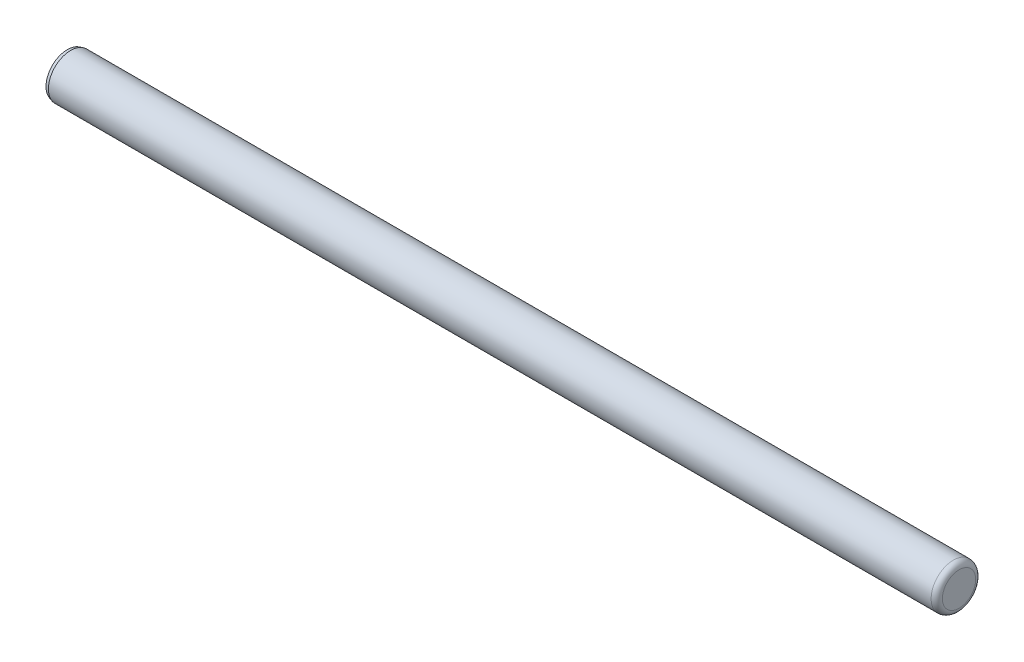
SolidWorks part; units mm, degrees
material "Alloy Steel"
ref_plane "Front" through (0, 0, 0) normal (0, 0, 1) x (1, 0, 0)
ref_plane "Top" through (0, 0, 0) normal (0, 1, 0) x (1, 0, 0)
ref_plane "Right" through (0, 0, 0) normal (1, 0, 0) x (0, 0, -1)
sketch "Sketch1" plane through (0, 0, 0) normal (1, 0, 0) x (0, 0, -1)
  circle A0 centre (0, 0) radius 6.35 construction
  point P3 (0, 6.35)
  dimension "Diameter" = 12.7
sketch "Sketch2" plane through (0, 0, 0) normal (0, 0, 1) x (1, 0, 0)
  line L0 (-127, 0) -> (127, 0) construction
  line L1 (127, 4.7498) -> (127, -0.6481) construction
  line L2 (-127, 6.0769) -> (-127, -6.0769) construction
  line L3 (-127, 6.0769) -> (-127, 6.35) construction
  line L4 (-127, -6.0769) -> (-127, -6.35) construction
  line L5 (-127, 6.0769) -> (-126.0478, 6.35) construction
  line L6 (-126.0478, 6.35) -> (125.3998, 6.35) construction
  arc A0 (125.3998, 6.35) -> (127, 4.7498) centre (125.3998, 4.7498) cw construction
  point P6 (-114.3, 0)
  point P8 (114.3, 0)
  point P23 (122.7582, 6.35)
  dimension "Crown Radius" = 1.6002
  dimension "Length" = 254
  dimension "D1" = 12.7
  dimension "D2" = 12.7
  dimension "Point Diameter" = 12.1539
  dimension "D3" = 16
  dimension "Crown Height" = 4.2418
sketch "Sketch3" plane through (0, 0, 0) normal (0, 0, 1) x (1, 0, 0)
  line L0 (127, 4.7498) -> (127, -0.6481) construction
  line L1 (-126.0478, 6.35) -> (125.3998, 6.35) construction
  line L2 (-127, 6.0769) -> (-126.0478, 6.35) construction
  line L3 (-127, 6.0769) -> (-127, -6.0769) construction
  line L4 (-127, 0) -> (127, 0) construction
  line L5 (127, 4.7498) -> (127, 0)
  line L6 (-126.0478, 6.35) -> (125.3998, 6.35)
  line L7 (-127, 6.0769) -> (-126.0478, 6.35)
  line L8 (-127, 6.0769) -> (-127, 0)
  line L9 (-127, 0) -> (127, 0)
  arc A0 (127, 4.7498) -> (125.3998, 6.35) centre (125.3998, 4.7498) ccw construction
  arc A1 (127, 4.7498) -> (125.3998, 6.35) centre (125.3998, 4.7498) ccw
revolve "Revolve1" add sketch "Sketch3" angle 360 about L0
equation "\"D1@Sketch2\" = \"Diameter@Sketch1\""
equation "\"D2@Sketch2\" = \"Diameter@Sketch1\""
